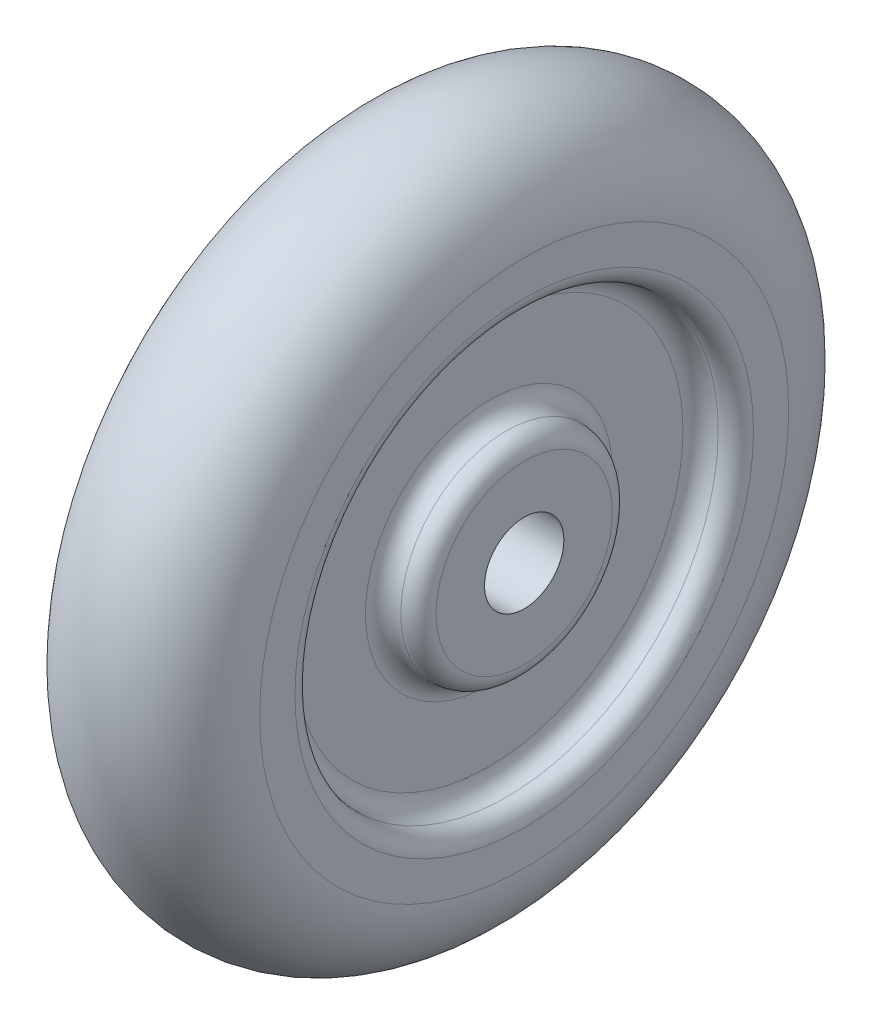
SolidWorks part; units mm, degrees
ref_plane "Front Plane" through (0, 0, 0) normal (0, 0, 1) x (1, 0, 0)
ref_plane "Top Plane" through (0, 0, 0) normal (0, 1, 0) x (1, 0, 0)
ref_plane "Right Plane" through (0, 0, 0) normal (1, 0, 0) x (0, 0, -1)
sketch "Sketch1" plane through (0, 0, 0) normal (0, 0, 1) x (1, 0, 0)
  line L0 (0, 0) -> (-6.4727, 0) construction
  line L1 (0, 0) -> (0, 15) construction
  line L2 (0, 20) -> (0, 15) construction
  line L4 (-5, 15) -> (-5, 2.25)
  line L5 (-5, 2.25) -> (5, 2.25)
  line L6 (5, 15) -> (5, 2.25)
  arc A0 (5, 15) -> (-5, 15) centre (0, 15) ccw
  point P9 (0, 0)
  dimension "D1" = 5
  dimension "D2" = 2.25
  dimension "D3" = 20
revolve "Revolve1" add sketch "Sketch1" angle 360 about L0
sketch "Sketch2" plane through (5, 0, 0) normal (1, 0, 0) x (0, 0, -1)
  circle A0 centre (0, 0) radius 6
  circle A1 centre (0, 0) radius 12
extrude "Cut-Extrude1" cut sketch "Sketch2" against normal blind 2
fillet "Fillet3" radius 1 4 edges at (3, 0, -12) (3, 0, -6) (5, 0, -6) (5, 0, -12)
mirror "Mirror2" about plane through (0, 0, 0) normal (1, 0, 0) of "Cut-Extrude1", "Fillet3"
